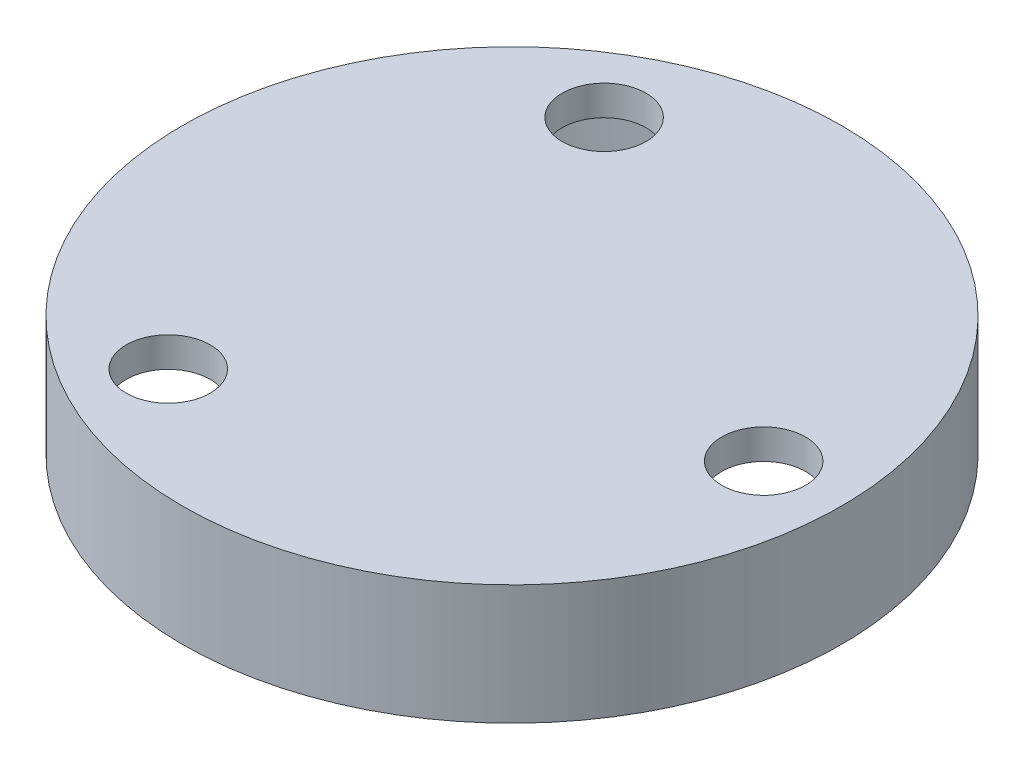
SolidWorks part; units mm, degrees
ref_plane "Front Plane" through (0, 0, 0) normal (0, 0, 1) x (1, 0, 0)
ref_plane "Top Plane" through (0, 0, 0) normal (0, 1, 0) x (1, 0, 0)
ref_plane "Right Plane" through (0, 0, 0) normal (1, 0, 0) x (0, 0, -1)
sketch "Sketch1" plane through (0, 0, 0) normal (0, 1, 0) x (1, 0, 0)
  circle A0 centre (0, 0) radius 55
  circle A1 centre (42, 0) radius 7
  circle A2 centre (-21, -36.3731) radius 7
  circle A3 centre (-21, 36.3731) radius 7
  point P5 (-29.8936, 33.31)
  point P7 (0, 0)
  point P12 (0, 0)
  dimension "D1" = 110
  dimension "D2" = 14
  dimension "D3" = 42
  dimension "D4" = 3
extrude "Boss-Extrude1" add sketch "Sketch1" along normal mid plane 20 contours A0 A3 A2 A1 | A2 | A3 | A1 region at (0, 0, 0) region at (42, 0, 0) region at (-21, 0, 36.3731) region at (-21, 0, -36.3731)
shell "Shell1" thickness 5 removed face at (0, -10, 55)
extrude "Cut-Extrude3" cut sketch "Sketch1<4>" against normal through all both and the other way through all contours A3 | A1 | A2 region at (42, 0, 0) region at (-21, 0, 36.3731) region at (-21, 0, -36.3731)
sketch "Sketch1<4>" plane through (0, 0, 0) normal (0, 1, 0) x (1, 0, 0) same geometry as "Sketch1"
